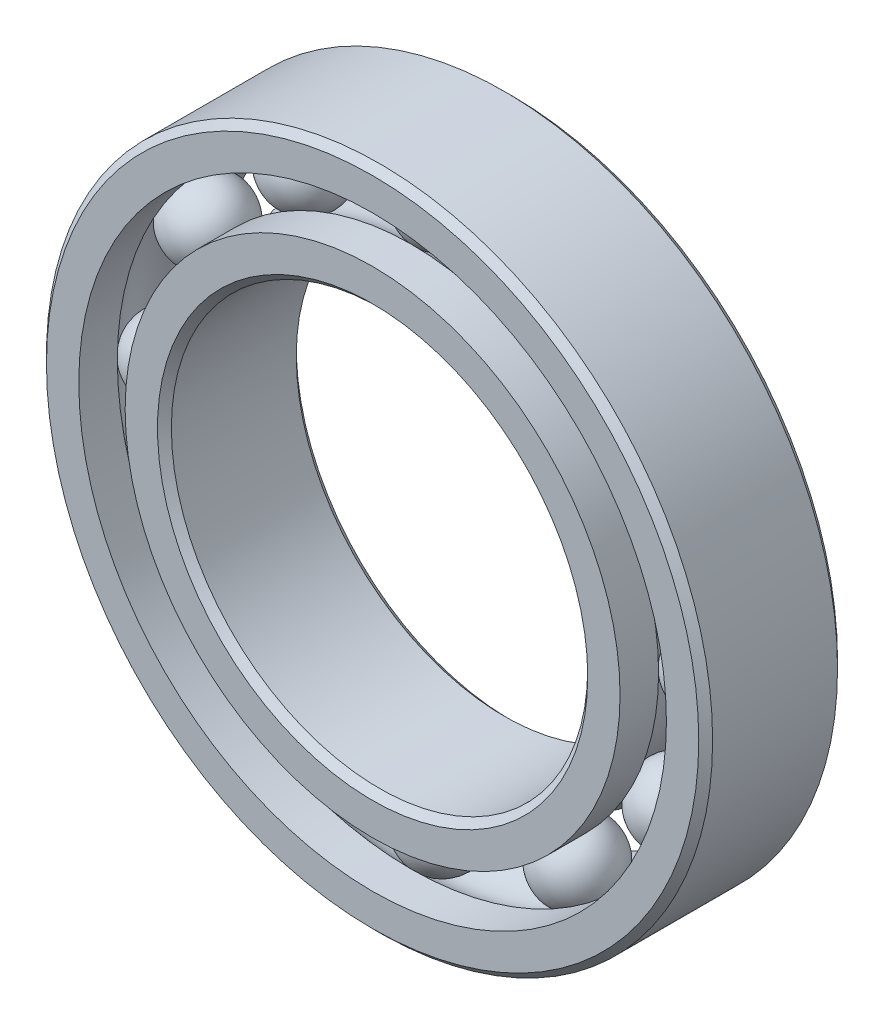
SolidWorks part; units mm, degrees
ref_plane "Front Plane" through (0, 0, 0) normal (0, 0, 1) x (1, 0, 0)
ref_plane "Top Plane" through (0, 0, 0) normal (0, 1, 0) x (1, 0, 0)
ref_plane "Right Plane" through (0, 0, 0) normal (1, 0, 0) x (0, 0, -1)
sketch "Sketch1" plane through (0, 0, 0) normal (1, 0, 0) x (0, 0, -1)
  line L0 (-2.5, 0) -> (2.5, 0) construction
  line L1 (0, 12) -> (0, -12) construction
  line L2 (2.25, 12) -> (-2.25, 12)
  line L3 (-2.25, 12) -> (-2.5, 11.75)
  line L4 (-2.5, 11.75) -> (-2.5, 10.5852)
  line L5 (-2.5, 10.5852) -> (-1.1111, 10.5852)
  line L6 (2.5, 10.5852) -> (1.1111, 10.5852)
  line L7 (2.5, 11.75) -> (2.5, 10.5852)
  line L8 (2.25, 12) -> (2.5, 11.75)
  line L9 (0, 12) -> (0, 9.75) construction
  line L10 (0, 9.75) -> (0, 7.5) construction
  arc A0 (-1.1111, 10.5852) -> (1.1111, 10.5852) centre (0, 9.75) cw
  point P14 (0, 7.5)
  dimension "Width" = 5
  dimension "OD" = 24
  dimension "D1" = 45
  dimension "D2" = 0.25
  dimension "Shaft Dia" = 15
  dimension "D3" = 2.2222
  dimension "D4" = 0.8352
revolve "Revolve1" add sketch "Sketch1" angle 360 about L0
sketch "Sketch3" plane through (0, 0, 0) normal (1, 0, 0) x (0, 0, -1)
  line L0 (-2.5, 8.9148) -> (-1.1111, 8.9148)
  line L1 (0, 12) -> (0, -12) construction
  line L2 (-2.5, 11.75) -> (-2.5, 10.5852) construction
  line L3 (-2.5, 8.9148) -> (-2.5, 7.75)
  line L4 (-2.25, 12) -> (-2.5, 11.75) construction
  line L5 (-2.5, 7.75) -> (-2.25, 7.5)
  line L6 (-2.25, 7.5) -> (2.25, 7.5)
  line L7 (2.25, 12) -> (2.25, -12) construction
  line L8 (2.25, 7.5) -> (2.5, 7.75)
  line L9 (2.5, -11.75) -> (2.5, 11.75) construction
  line L10 (2.5, 7.75) -> (2.5, 8.9148)
  line L11 (2.5, 8.9148) -> (1.1111, 8.9148)
  line L13 (2.25, 12) -> (2.5, 11.75) construction
  arc A0 (1.1111, 10.5852) -> (-1.1111, 10.5852) centre (0, 9.75) ccw construction
  arc A1 (1.1111, 8.9148) -> (-1.1111, 8.9148) centre (0, 9.75) cw
revolve "Revolve3" add sketch "Sketch3" angle 360 about L0
sketch "Sketch4" plane through (0, 0, 0) normal (1, 0, 0) x (0, 0, -1)
  line L0 (-1.39, 9.75) -> (1.39, 9.75)
  arc A2 (-1.39, 9.75) -> (1.39, 9.75) centre (0, 9.75) cw
  arc A3 (1.1111, 10.5852) -> (-1.1111, 10.5852) centre (0, 9.75) ccw construction
revolve "Revolve4" add sketch "Sketch4" angle 360 about L0
ref_axis "Axis1" through (0, 0, -2.5) along (0, 0, 1)
pattern_circular "CirPattern1" count 12 every 30 about axis through (0, 0, -2.5) along (0, 0, 1) of bodies 104
sketch "Sketch5" plane through (0, 0, 0) normal (1, 0, 0) x (0, 0, -1)
  line L0 (-2.5, 10.5852) -> (-1.1111, 10.5852) construction
  line L1 (-2.375, 10.5852) -> (-1.39, 10.5852)
  line L2 (-2.375, 10.5852) -> (-2.375, 8.9148)
  line L3 (-2.375, 8.9148) -> (-1.39, 8.9148)
  line L4 (-1.39, 10.5852) -> (-1.39, 8.9148)
  line L5 (-2.5, 8.9148) -> (-1.1111, 8.9148) construction
  line L6 (2.5, 10.5852) -> (1.1111, 10.5852) construction
  line L7 (2.375, 10.5852) -> (1.39, 10.5852)
  line L8 (2.375, 10.5852) -> (2.375, 8.9148)
  line L9 (2.375, 8.9148) -> (1.39, 8.9148)
  line L10 (1.39, 10.5852) -> (1.39, 8.9148)
  line L11 (2.5, 8.9148) -> (1.1111, 8.9148) construction
  line L12 (-2.25, 12) -> (-2.5, 11.75) construction
  point P18 (-2.375, 11.875)
equation "\"D2@Sketch1\" = \"Width@Sketch1\"*.05"
equation "\"D3@Sketch1\" = \"Width@Sketch1\"/2.25"
equation "\"D4@Sketch1\" = (((\"OD@Sketch1\"-\"Width@Sketch1\")/2)/3.25)/3.5"
equation "\"D2@CirPattern1\" = 360/\"Balls@CirPattern1\""
